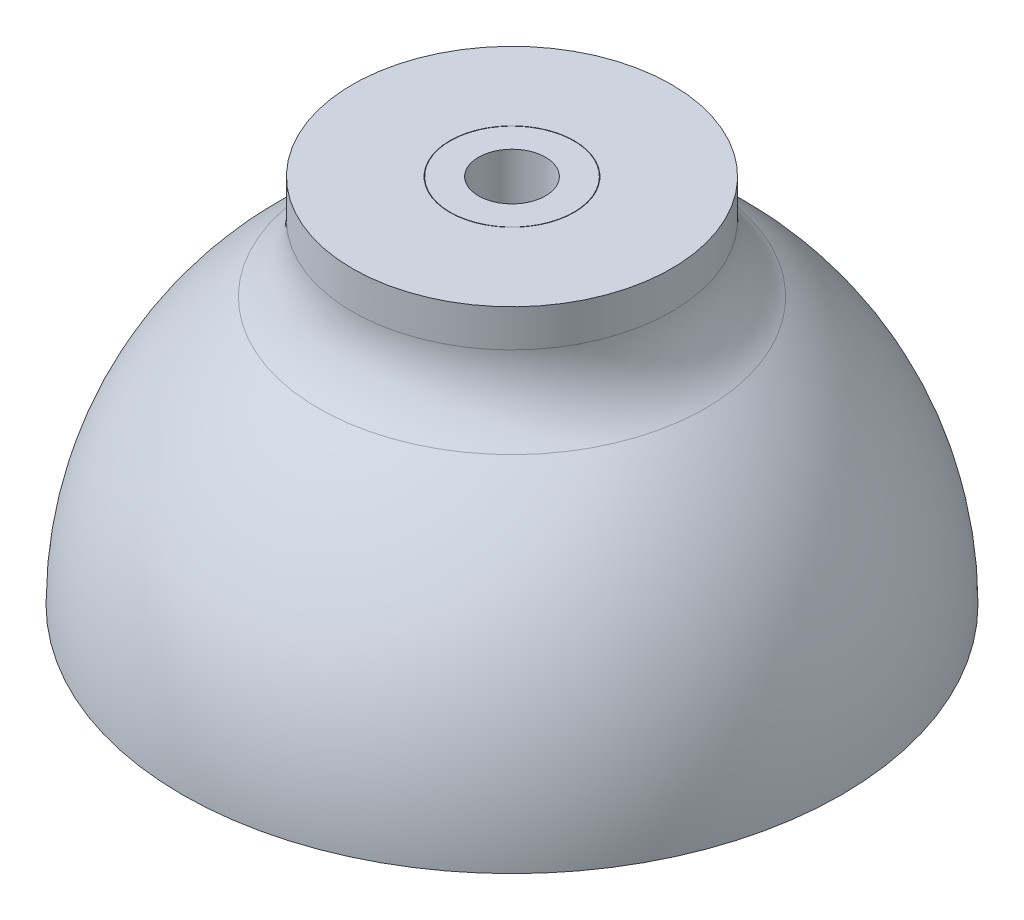
SolidWorks part; units mm, degrees
ref_plane "Ebene vorne" through (0, 0, 0) normal (0, 0, 1) x (1, 0, 0)
ref_plane "Ebene oben" through (0, 0, 0) normal (0, 1, 0) x (1, 0, 0)
ref_plane "Ebene rechts" through (0, 0, 0) normal (1, 0, 0) x (0, 0, -1)
sketch "Skizze1" plane through (0, 0, 0) normal (0, 0, 1) x (1, 0, 0)
  line L0 (0, 30) -> (0, 40)
  line L1 (-30, 0) -> (-40, 0)
  arc A0 (0, 30) -> (-30, 0) centre (0, 0) ccw
  arc A1 (0, 40) -> (-40, 0) centre (0, 0) ccw
revolve "Rotation1" add sketch "Skizze1" angle 360 about L0
ref_plane "Ebene13" through (0, 35, 0) normal (0, 1, 0) x (1, 0, 0)
sketch "Skizze14" plane through (0, 35, 0) normal (0, 1, 0) x (1, 0, 0)
  circle A0 centre (0, 0) radius 19.3649
  circle A1 centre (0, 0) radius 19.3649
extrude "Aufsatz-Linear austragen1" add sketch "Skizze14" along normal blind 10
sketch "Skizze2" plane through (0, 0, 0) normal (0, 0, 1) x (1, 0, 0)
  line L0 (0, -30) -> (-5.1, -30)
  line L1 (-5.1, -30) -> (-5.1, 22.5211)
  line L2 (-5.1, 29.5633) -> (-9.4646, 28.4679)
  line L7 (-9.4646, 28.4679) -> (-18.3757, 23.7136)
  line L8 (44, 0) -> (-44, 0) construction
  arc A0 (30, 0) -> (-30, 0) centre (0, 0) ccw
  arc A1 (30, 0) -> (-30, 0) centre (0, 0) ccw construction
  dimension "D1" = 28.081
ref_axis "Achse1" through (0, -2, 0) along (0, 1, 0)
ref_axis "Achse2" through (0, 0, -44) along (0, 0, 1)
ref_plane "Ebene1" through (0, 0, 0) normal (-0.4707, 0.8823, 0) x (0, 0, 1)
ref_plane "Ebene2" through (-13.9187, 26.0894, 0) normal (-0.4707, 0.8823, 0) x (0, 0, 1)
sketch "Skizze3" plane through (-13.9187, 26.0894, 0) normal (-0.4707, 0.8823, 0) x (0, 0, 1)
  line L3 (0, 5.0494) -> (0, -5.0506) construction
  line L4 (0, 5.0494) -> (0, -5.0506) construction
  circle A3 centre (0, -0.0006) radius 5.05
extrude "Schnitt-Linear austragen1" cut sketch "Skizze3" along normal blind 6.8 and the other way blind 1
pattern_circular "Kreismuster1" count 8 every 45 about axis through (0, -2, 0) along (0, 1, 0) of "Schnitt-Linear austragen1"
ref_plane "Ebene3" through (0, 0, 0) normal (0.9239, 0, 0.3827) x (0, 1, 0)
ref_plane "Ebene4" through (0, 0, 0) normal (0.3827, 0, -0.9239) x (0, 1, 0)
ref_axis "Achse3" through (-18.2254, 0, 44) along (0.3827, 0, -0.9239)
sketch "Skizze5" plane through (0, 0, 0) normal (0.3827, 0, -0.9239) x (0, 1, 0)
  line L0 (30, 0) -> (24.6598, -17.0849)
  line L6 (0, -44) -> (0, 44) construction
  line L8 (24.6598, -17.0849) -> (17.5925, -24.3003)
  arc A1 (0, -30) -> (0, 30) centre (0, 0) ccw construction
  dimension "D1" = 44.406
ref_plane "Ebene5" through (0, 0, 0) normal (-0.6465, 0.7144, -0.2678) x (0.3827, 0, -0.9239)
ref_plane "Ebene6" through (-19.1176, 21.1233, -7.9188) normal (-0.6465, 0.7144, -0.2678) x (0.3827, 0, -0.9239)
sketch "Skizze6" plane through (-19.1176, 21.1233, -7.9188) normal (-0.6465, 0.7144, -0.2678) x (0.3827, 0, -0.9239)
  line L2 (0, -5.0521) -> (0, 5.0479) construction
  line L3 (0, -5.0521) -> (0, 5.0479) construction
  circle A2 centre (0, -0.0021) radius 5.05
extrude "Schnitt-Linear austragen2" cut sketch "Skizze6" along normal blind 6.8 and the other way blind 6.8
pattern_circular "Kreismuster2" count 8 every 45 about axis through (0, -2, 0) along (0, 1, 0) of "Schnitt-Linear austragen2"
sketch "Skizze7" plane through (0, 0, 0) normal (0, 0, 1) x (1, 0, 0)
  line L0 (-18.3757, 23.7136) -> (-21.785, 20.6255)
  line L3 (-21.785, 20.6255) -> (-27.3953, 12.227)
  line L4 (44, 0) -> (-44, 0) construction
  arc A1 (30, 0) -> (-30, 0) centre (0, 0) ccw construction
  dimension "D1" = 56.257
ref_plane "Ebene7" through (0, 0, 0) normal (-0.8316, 0.5554, 0) x (0, 0, 1)
ref_plane "Ebene8" through (-24.5894, 16.4239, 0) normal (-0.8316, 0.5554, 0) x (0, 0, 1)
sketch "Skizze8" plane through (-24.5894, 16.4239, 0) normal (-0.8316, 0.5554, 0) x (0, 0, 1)
  line L1 (0, 5.0515) -> (0, -5.0485) construction
  line L2 (0, 5.0515) -> (0, -5.0485) construction
  circle A1 centre (0, 0.0015) radius 5.05
extrude "Schnitt-Linear austragen3" cut sketch "Skizze8" against normal blind 6.8 and the other way blind 6.8
pattern_circular "Kreismuster3" count 8 every 45 about axis through (0, -2, 0) along (0, 1, 0) of "Schnitt-Linear austragen3"
sketch "Skizze9" plane through (0, 0, 0) normal (0.3827, 0, -0.9239) x (0, 1, 0)
  line L0 (17.5925, 24.3003) -> (17.0207, 24.7041)
  line L1 (17.0207, 24.7041) -> (7.8577, 28.9526)
  line L2 (0, -44) -> (0, 44) construction
  arc A0 (0, -30) -> (0, 30) centre (0, 0) ccw construction
  arc A1 (0, -30) -> (0, 30) centre (0, 0) ccw construction
  dimension "D1" = 65.125
ref_plane "Ebene9" through (0, 0, 0) normal (0.8381, 0.4207, 0.3472) x (0.3827, 0, -0.9239)
ref_plane "Ebene10" through (24.7837, 12.4407, 10.2657) normal (0.8381, 0.4207, 0.3472) x (0.3827, 0, -0.9239)
sketch "Skizze10" plane through (24.7837, 12.4407, 10.2657) normal (0.8381, 0.4207, 0.3472) x (0.3827, 0, -0.9239)
  line L0 (0, 5.0475) -> (0, -5.0525) construction
  line L1 (0, 5.0475) -> (0, -5.0525) construction
  circle A0 centre (0, -0.0025) radius 5.05
extrude "Schnitt-Linear austragen4" cut sketch "Skizze10" against normal blind 6.8 and the other way blind 6.8
pattern_circular "Kreismuster4" count 8 every 45 about axis through (0, -2, 0) along (0, 1, 0) of "Schnitt-Linear austragen4"
sketch "Skizze11" plane through (0, 0, 0) normal (0, 0, 1) x (1, 0, 0)
  line L0 (27.3953, 12.227) -> (27.6731, 11.5845)
  line L1 (27.6731, 11.5845) -> (29.9492, 1.7443)
  line L2 (44, 0) -> (-44, 0) construction
  arc A0 (30, 0) -> (-30, 0) centre (0, 0) ccw construction
  arc A1 (30, 0) -> (-30, 0) centre (0, 0) ccw construction
  dimension "D1" = 76.976
ref_plane "Ebene11" through (0, 0, 0) normal (0.9743, 0.2253, 0) x (0, 0, 1)
ref_plane "Ebene12" through (28.8098, 6.6619, 0) normal (0.9743, 0.2253, 0) x (0, 0, 1)
sketch "Skizze12" plane through (28.8098, 6.6619, 0) normal (0.9743, 0.2253, 0) x (0, 0, 1)
  line L0 (0, -5.0522) -> (0, 5.0478) construction
  line L1 (0, -5.0522) -> (0, 5.0478) construction
  circle A0 centre (0, -0.0022) radius 5.05
extrude "Schnitt-Linear austragen5" cut sketch "Skizze12" against normal blind 6.8 and the other way blind 6.8
pattern_circular "Kreismuster5" count 8 every 45 about axis through (0, -2, 0) along (0, 1, 0) of "Schnitt-Linear austragen5"
sketch "Skizze13" plane through (0, 0, 0) normal (0, 1, 0) x (1, 0, 0)
  circle A0 centre (0, 0) radius 7.55
extrude "Schnitt-Linear austragen6" cut sketch "Skizze13" along normal blind 56.8
fillet "Verrundung1" radius 1 1 edges at (0, 29.0344, -7.55)
fillet "Verrundung2" radius 10 1 edges at (0, 35, 19.3649)
sketch "Skizze15" plane through (0, 0, 0) normal (0, 0, 1) x (1, 0, 0)
  line L0 (-7.55, 29.7976) -> (-7.55, 45)
  line L1 (7.55, 45) -> (7.55, 29.7976)
  line L2 (7.55, 45) -> (7.55, 29.7976)
  arc A0 (30, 0) -> (-30, 0) centre (0, 0) ccw construction
  arc A1 (30, 0) -> (8.2742, 28.8364) centre (0, 0) ccw
  arc A2 (-8.2742, 28.8364) -> (-7.55, 29.7976) centre (-8.55, 29.7976) ccw
  arc A3 (7.55, 29.7976) -> (8.2742, 28.8364) centre (8.55, 29.7976) ccw
  arc A4 (7.55, 29.7976) -> (8.2742, 28.8364) centre (8.55, 29.7976) ccw
sketch "Skizze16" plane through (0, 0, 0) normal (0, 0, 1) x (1, 0, 0)
  line L4 (7.5, 28.8364) -> (4.07, 28.8364)
  line L7 (4.07, 45) -> (7.5, 45)
  line L8 (7.5, 45) -> (7.5, 29.7976)
  line L9 (7.5, 29.7976) -> (7.5, 28.8364)
  line L10 (0, 46.1023) -> (0, 27.5773) construction
  line L11 (4.07, 45) -> (4.07, 28.8364)
  line L12 (0, -41.25) -> (0, 41.25) construction
revolve "Rotation2" add sketch "Skizze16" angle 360 about L10
